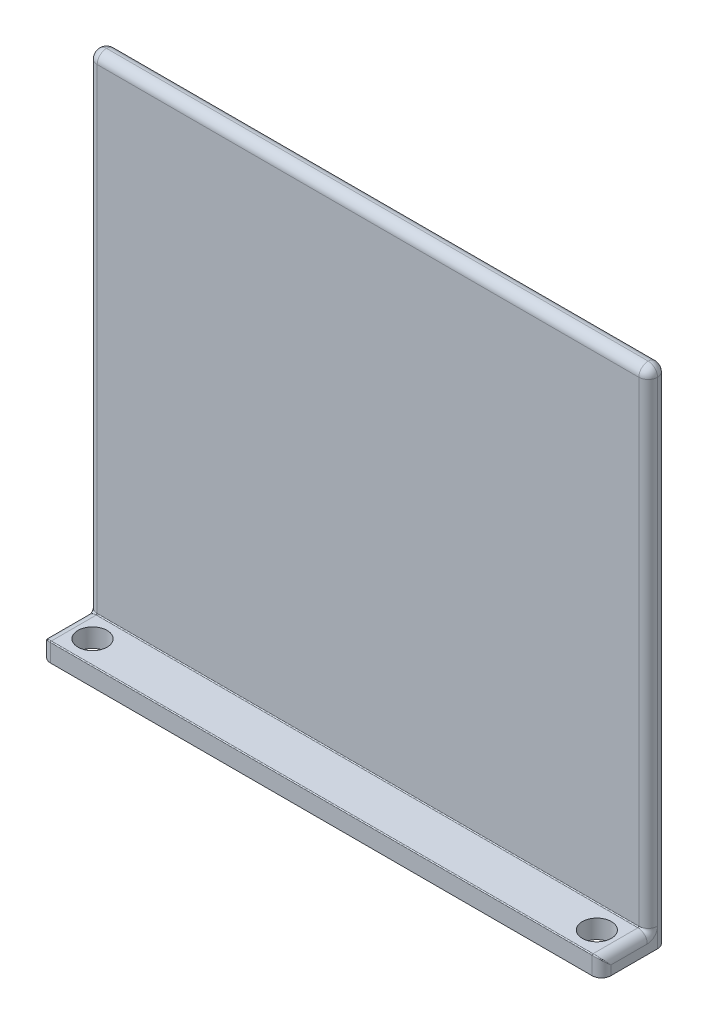
SolidWorks part; units mm, degrees
ref_plane "Front Plane" through (0, 0, 0) normal (0, 0, 1) x (1, 0, 0)
ref_plane "Top Plane" through (0, 0, 0) normal (0, 1, 0) x (1, 0, 0)
ref_plane "Right Plane" through (0, 0, 0) normal (1, 0, 0) x (0, 0, -1)
sketch "Sketch1" plane through (0, 0, 0) normal (0, 0, 1) x (1, 0, 0)
  line L1 (-30, -27) -> (30, -27)
  line L2 (-30, -27) -> (-30, 27)
  line L3 (-30, 27) -> (30, 27)
  line L4 (30, -27) -> (30, 27)
  line L5 (-30, -27) -> (30, 27) construction
  line L6 (-30, 27) -> (30, -27) construction
  point P0 (0, 0)
  dimension "D1" = 60
  dimension "D2" = 54
extrude "Boss-Extrude1" add sketch "Sketch1" along normal blind 2
sketch "Sketch2" plane through (0, 0, 2) normal (0, 0, 1) x (1, 0, 0)
  line L0 (30, -27) -> (30, 27) construction
  line L1 (-30, -27) -> (30, -27)
  line L2 (-30, -27) -> (-30, -25)
  line L3 (-30, -25) -> (30, -25)
  line L4 (30, -27) -> (30, -25)
  dimension "D1" = 2
extrude "Boss-Extrude2" add sketch "Sketch2" along normal blind 5
sketch "Sketch3" plane through (0, -25, 0) normal (0, 1, 0) x (1, 0, 0)
  line L0 (30, -7) -> (30, -2) construction
  line L1 (0, 0) -> (0, -7) construction
  line L2 (30, -7) -> (-30, -7) construction
  circle A0 centre (27, -4.5) radius 1.56
  circle A1 centre (-27, -4.5) radius 1.56
  point P5 (30, -4.5)
  dimension "D1" = 3.12
  dimension "D2" = 3
extrude "Cut-Extrude1" cut sketch "Sketch3" against normal blind 5
fillet "Fillet1" radius 0.1 1 edges at (0, -25, 2)
fillet "Fillet2" radius 1 12 edges at (30, -25, 4.55) (30, -24.9707, 2.0293) (-30, -25, 4.55) (-30, -24.9707, 2.0293) (30, 0, 0) (-30, 0, 0) (0, 27, 0) (0, 27, 2) (30, 1.05, 2) (-30, 1.05, 2) (-30, -26, 7) (30, -26, 7)
fillet "Fillet3" radius 0.1 3 edges at (29.7071, -25.2929, 6.7071) (-29.7071, -25.2929, 6.7071) (0, -25, 7)
